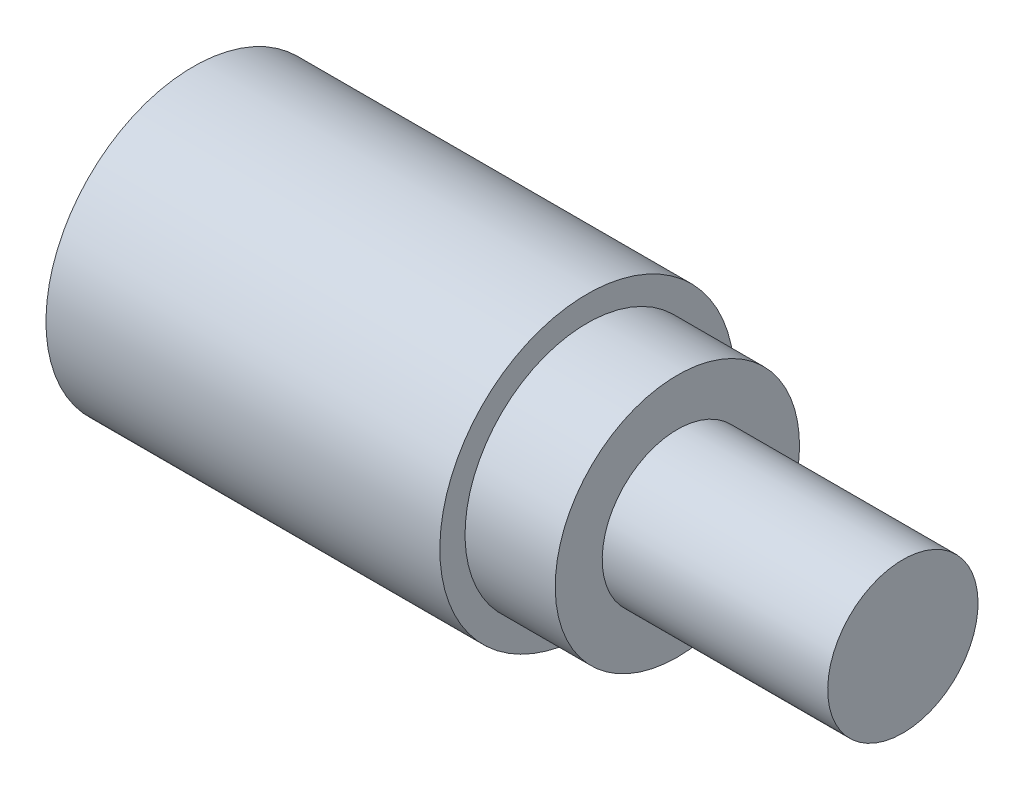
SolidWorks part; units mm, degrees
ref_plane "XY" through (0, 0, 0) normal (0, 0, 1) x (1, 0, 0)
ref_plane "XZ" through (0, 0, 0) normal (0, 1, 0) x (1, 0, 0)
ref_plane "YZ" through (0, 0, 0) normal (1, 0, 0) x (0, 0, -1)
ref_axis "X" through (-88.99, 0, 0) along (1, 0, 0)
ref_axis "Y" through (0, -55, 0) along (0, 1, 0)
ref_axis "Z" through (0, 0, 55) along (0, 0, -1)
sketch "Sketch1" plane through (0, 0, 0) normal (0, 0, 1) x (1, 0, 0)
  line L0 (0, 0) -> (0, 6.35) construction
  line L1 (0, 10.3187) -> (-7.62, 10.3187)
  line L2 (-7.62, 10.3187) -> (-7.62, 12.446)
  line L3 (-7.62, 12.446) -> (-40.894, 12.446)
  line L4 (-40.894, 12.446) -> (-40.894, 0)
  line L5 (-40.894, 0) -> (19.05, 0)
  line L6 (19.05, 0) -> (19.05, 6.35)
  line L7 (19.05, 6.35) -> (0, 6.35)
  line L8 (0, 6.35) -> (0, 10.3187)
  dimension "D1" = 40.894
  dimension "D2" = 6.35
  dimension "D3" = 12.446
  dimension "D4" = 10.3187
  dimension "D5" = 7.62
  dimension "D6" = 19.05
revolve "Revolve1" add sketch "Sketch1" angle 360 about L5
